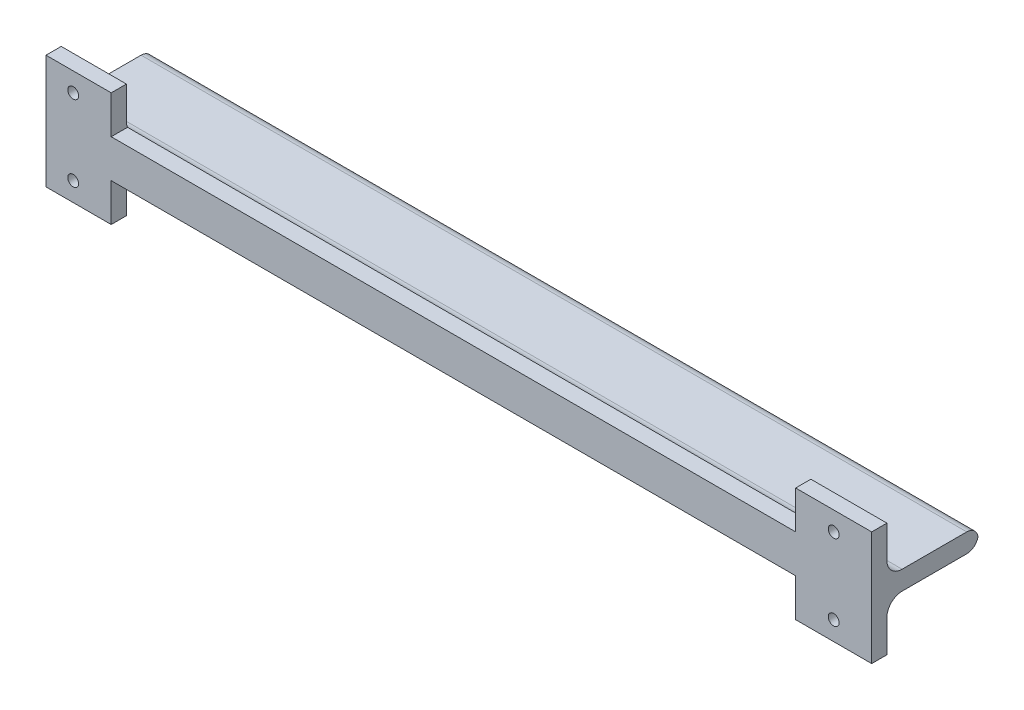
SolidWorks part; units mm, degrees
ref_plane "Front Plane" through (0, 0, 0) normal (0, 0, 1) x (1, 0, 0)
ref_plane "Top Plane" through (0, 0, 0) normal (0, 1, 0) x (1, 0, 0)
ref_plane "Right Plane" through (0, 0, 0) normal (1, 0, 0) x (0, 0, -1)
sketch "Sketch1" plane through (0, 0, 0) normal (0, 0, 1) x (1, 0, 0)
  line L0 (-100, 10) -> (-100, -10) construction
  line L6 (110, -15) -> (90, -15)
  line L7 (-100, -10) -> (-90, -10) construction
  line L8 (100, -10) -> (100, 10) construction
  line L9 (100, 10) -> (90, 10) construction
  line L10 (-107.15, -15) -> (-107.15, 15)
  line L11 (-107.15, 15) -> (-90, 15)
  line L13 (110, 15) -> (110, -15)
  line L14 (90, 15) -> (90, 5)
  line L15 (90, 5) -> (-90, 5)
  line L16 (-90, 5) -> (-90, 15)
  line L17 (90, 15) -> (110, 15)
  line L18 (-90, 10) -> (-100, 10) construction
  line L19 (90, -15) -> (90, -5)
  line L20 (90, -5) -> (-90, -5)
  line L21 (-90, -5) -> (-90, -15)
  line L22 (-90, -15) -> (-107.15, -15)
  line L23 (90, -10) -> (100, -10) construction
  circle A0 centre (100, 10) radius 1.425
  circle A1 centre (100, -10) radius 1.425
  circle A2 centre (-100, -10) radius 1.425
  circle A3 centre (-100, 10) radius 1.425
  point P0 (0, 0)
  point P15 (-100, 0)
  point P19 (0, 5)
  dimension "D5" = 5
  dimension "D6" = 10
  dimension "D7" = 10
  dimension "D4" = 5
  dimension "D1" = 20
  dimension "D2" = 200
  dimension "D3" = 217.15
  dimension "D8" = 180
  dimension "D9" = 10
  dimension "D10" = 180
extrude "Boss-Extrude1" add sketch "Sketch1" against normal blind 4
sketch "Sketch2" plane through (0, 0, -4) normal (0, 0, -1) x (-1, 0, 0)
  line L0 (107.15, 2.5) -> (-110, 2.5)
  line L2 (107.15, 15) -> (107.15, -15) construction
  line L3 (-110, -15) -> (-110, 15) construction
  line L4 (-110, 2.5) -> (-110, -2.5)
  line L5 (-110, -2.5) -> (107.15, -2.5)
  line L6 (107.15, -2.5) -> (107.15, 2.5)
  point P7 (-110, 0)
  point P10 (-110, 0)
  dimension "D1" = 5
extrude "Boss-Extrude2" add sketch "Sketch2" along normal blind 24 contours L0 L4 L5 L6
fillet "Fillet1" radius 4 2 edges at (1.425, 2.5, -4) (1.425, -2.5, -4)
fillet "Fillet2" radius 3 2 edges at (1.425, -2.5, -28) (1.425, 2.5, -28)
